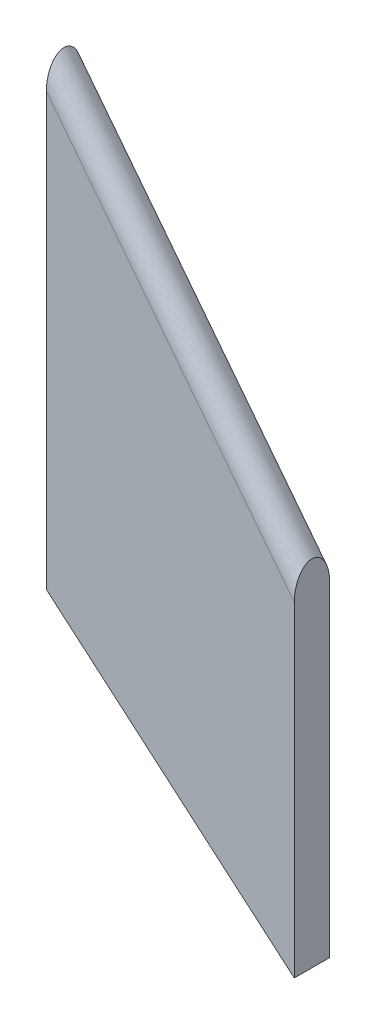
SolidWorks part; units mm, degrees
ref_plane "Front Plane" through (0, 0, 0) normal (0, 0, 1) x (1, 0, 0)
ref_plane "Top Plane" through (0, 0, 0) normal (0, 1, 0) x (1, 0, 0)
ref_plane "Right Plane" through (0, 0, 0) normal (1, 0, 0) x (0, 0, -1)
sketch "Sketch1" plane through (0, 0, 0) normal (0, 0, 1) x (1, 0, 0)
  line L0 (0, 0) -> (0, 41.275)
  line L1 (0, 41.275) -> (22.225, 12.7)
  line L2 (22.225, 12.7) -> (22.225, -19.05)
  line L3 (22.225, -19.05) -> (0, 0)
  dimension "D1" = 22.225
  dimension "D2" = 41.275
  dimension "D3" = 28.575
  dimension "D4" = 60.325
extrude "Boss-Extrude1" add sketch "Sketch1" along normal blind 1.5875 and the other way blind 1.5875 contours L3 L0 L1 L2
fillet "Fillet1" 2 edges at (11.1125, 26.9875, 1.5875) (11.1125, 26.9875, -1.5875) type full round first side face at (11.1125, 8.7312, 1.5875) second side face at (11.1125, 8.7312, -1.5875) middle face at (11.1125, 26.9875, 0)
